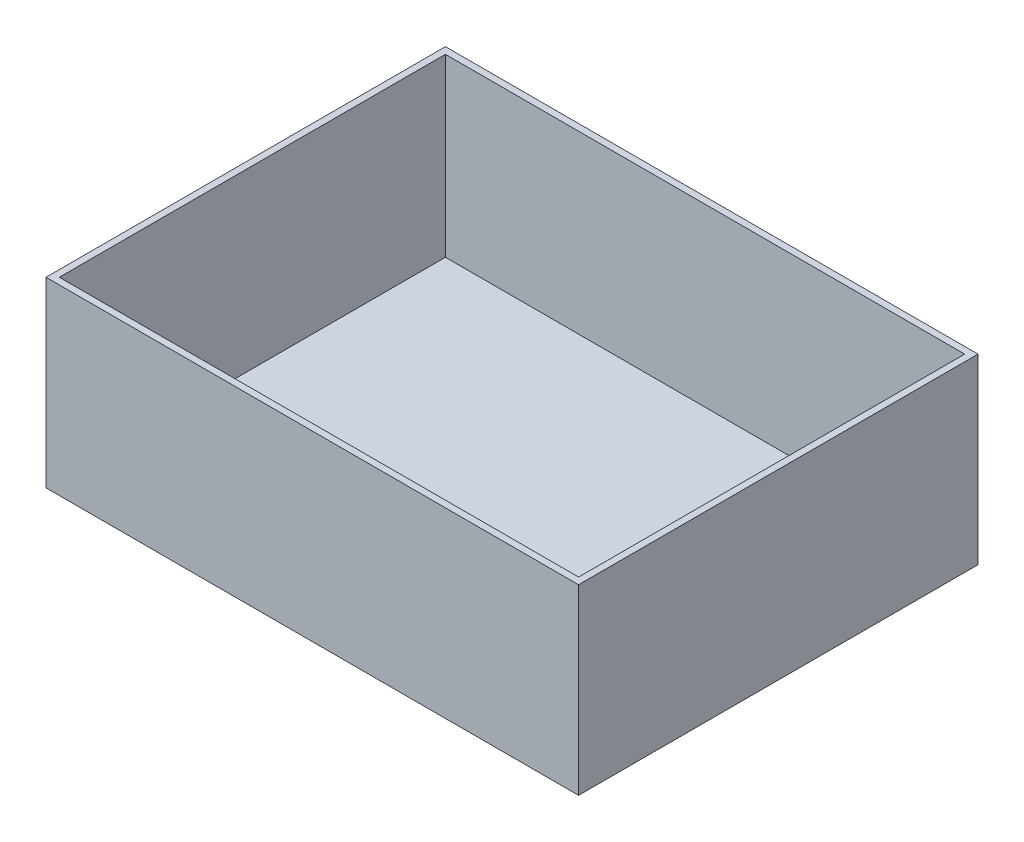
SolidWorks part; units mm, degrees
other "Magic Base"
ref_plane "Front Plane" through (0, 0, 0) normal (0, 0, 1) x (1, 0, 0)
ref_plane "Top Plane" through (0, 0, 0) normal (0, 1, 0) x (1, 0, 0)
ref_plane "Right Plane" through (0, 0, 0) normal (1, 0, 0) x (0, 0, -1)
sketch "Sketch1" plane through (0, 0, 0) normal (0, 1, 0) x (1, 0, 0)
  line L1 (-100, 75) -> (100, 75)
  line L2 (-100, 75) -> (-100, -75)
  line L3 (-100, -75) -> (100, -75)
  line L4 (100, 75) -> (100, -75)
  line L5 (-100, 75) -> (100, -75) construction
  line L6 (-100, -75) -> (100, 75) construction
  point P0 (0, 0)
  dimension "D1" = 200
  dimension "D2" = 150
extrude "Boss-Extrude1" add sketch "Sketch1" along normal blind 68.5
sketch "Sketch2" plane through (0, 68.5, 0) normal (0, 1, 0) x (1, 0, 0)
  line L0 (100, -75) -> (100, 75) construction
  line L1 (-97.5, 72.5) -> (97.5, 72.5)
  line L2 (-97.5, 72.5) -> (-97.5, -72.5)
  line L3 (-97.5, -72.5) -> (97.5, -72.5)
  line L4 (97.5, 72.5) -> (97.5, -72.5)
  line L5 (-97.5, 72.5) -> (97.5, -72.5) construction
  line L6 (-97.5, -72.5) -> (97.5, 72.5) construction
  line L7 (100, 75) -> (-100, 75) construction
  point P0 (0, 0)
  dimension "D1" = 2.5
  dimension "D2" = 2.5
extrude "Cut-Extrude1" cut sketch "Sketch2" against normal blind 66
equation "\"boxWidth\" = 15cm"
equation "\"boxTall\" = 20cm"
equation "\"boxHeight\" =68.5cm"
equation "\"DisplayHeight\"= 18mm"
equation "\"DisplayWidth\"= 93mm"
equation "\"DisplayTall\"= 97mm"
